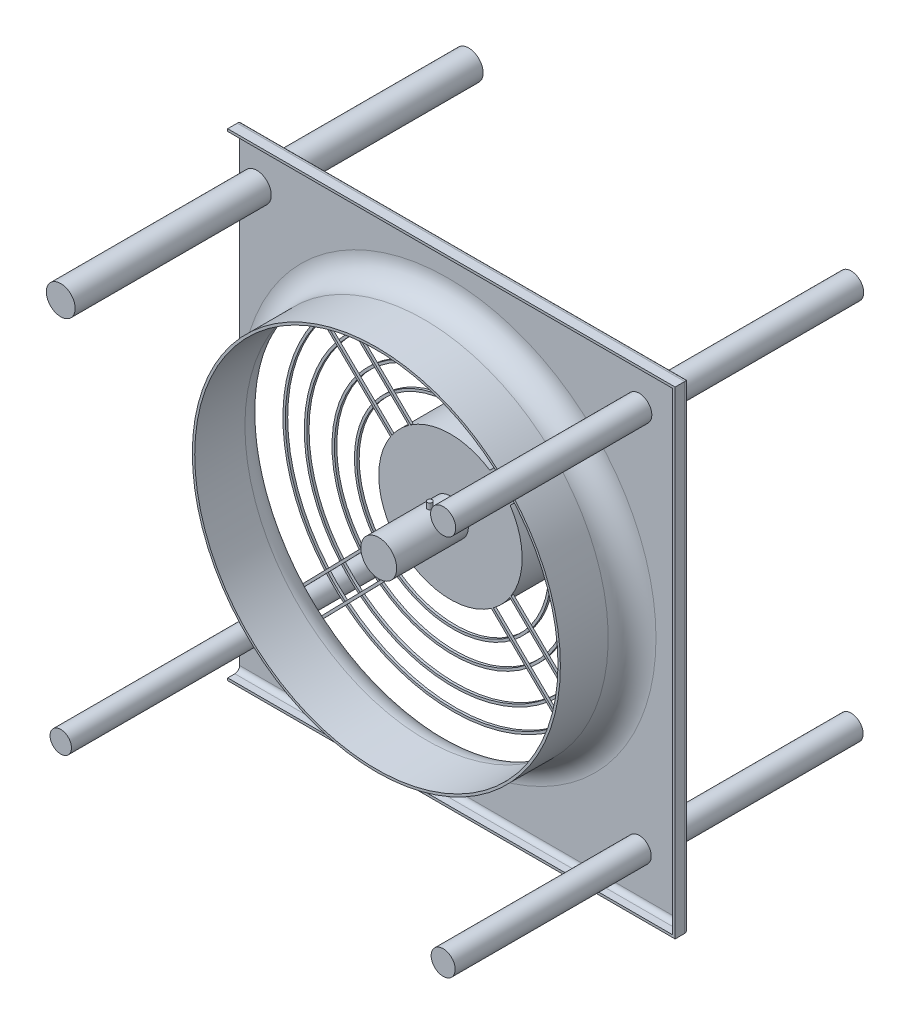
SolidWorks part; units mm, degrees
ref_plane "Front Plane" through (0, 0, 0) normal (0, 0, 1) x (1, 0, 0)
ref_plane "Top Plane" through (0, 0, 0) normal (0, 1, 0) x (1, 0, 0)
ref_plane "Right Plane" through (0, 0, 0) normal (1, 0, 0) x (0, 0, -1)
sketch "Sketch1" plane through (0, 0, 0) normal (0, 0, 1) x (1, 0, 0)
  line L1 (-100, -100) -> (100, -100)
  line L2 (-100, -100) -> (-100, 100)
  line L3 (-100, 100) -> (100, 100)
  line L4 (100, -100) -> (100, 100)
  line L5 (-100, -100) -> (100, 100) construction
  line L6 (-100, 100) -> (100, -100) construction
  circle A0 centre (0, 0) radius 76
  point P0 (0, 0)
  dimension "D2" = 152
  dimension "D1" = 200
extrude "Boss-Extrude1" add sketch "Sketch1" along normal blind 1
sketch "Sketch2" plane through (0, 0, 1) normal (0, 0, 1) x (1, 0, 0)
  line L4 (100, -100) -> (100, 100)
  line L5 (100, 100) -> (-100, 100)
  line L6 (-100, 100) -> (-100, -100)
  line L7 (-100, -100) -> (100, -100)
  line L8 (100, -100) -> (100, 100)
  line L9 (100, 100) -> (-100, 100)
  line L10 (-100, 100) -> (-100, -100)
  line L11 (-100, -100) -> (100, -100)
  line L16 (99, -99) -> (99, 99)
  line L17 (99, 99) -> (-99, 99)
  line L18 (-99, 99) -> (-99, -99)
  line L19 (-99, -99) -> (99, -99)
  line L20 (99, -99) -> (99, 99)
  line L21 (99, 99) -> (-99, 99)
  line L22 (-99, 99) -> (-99, -99)
  line L23 (-99, -99) -> (99, -99)
  dimension "D1" = 0
  dimension "D2" = 1
extrude "Boss-Extrude2" add sketch "Sketch2" along normal blind 5
fillet "Fillet1" radius 2 4 edges at (0, -99, 1) (99, 0, 1) (0, 99, 1) (-99, 0, 1)
fillet "Fillet2" radius 2 4 edges at (-100, 0, 0) (0, 100, 0) (100, 0, 0) (0, -100, 0)
sketch "Sketch3" plane through (0, 0, 1) normal (0, 0, 1) x (1, 0, 0)
  circle A0 centre (0, 0) radius 76 construction
  circle A1 centre (0, 0) radius 76
  circle A4 centre (0, 0) radius 77
  circle A5 centre (0, 0) radius 77
  dimension "D1" = 1
extrude "Boss-Extrude3" add sketch "Sketch3" along normal blind 30
fillet "Fillet3" radius 10 2 edges at (76, 0, 0) (-77, 0, 1)
hole_wizard "Ø4.0 (4) Diameter Hole1" positions "Sketch5" profile "Sketch6" hole size "Ø4.0" standard "DIN" end condition through all
sketch "Sketch5" plane through (0, 0, 0) normal (0, 0, -1) x (-1, 0, 0)
  line L1 (-80, 80) -> (80, 80) construction
  line L2 (-80, 80) -> (-80, -80) construction
  line L3 (-80, -80) -> (80, -80) construction
  line L4 (80, 80) -> (80, -80) construction
  line L5 (-80, 80) -> (80, -80) construction
  line L6 (-80, -80) -> (80, 80) construction
  point P0 (80, 80)
  point P2 (80, -80)
  point P4 (-80, -80)
  point P6 (-80, 80)
  point P8 (0, 0)
  dimension "D1" = 160
sketch "Sketch6" plane through (-80, 80, 0) normal (1, 0, 0) x (0, 1, 0)
  line L0 (0, 0) -> (0, 31)
  line L1 (0, 31) -> (2, 31)
  line L2 (2, 31) -> (2, 0)
  line L5 (2, 0) -> (0, 0)
  line L11 (0, -6.35) -> (0, 107.95) construction
  dimension "Thru Hole Dia." = 4
  dimension "Thru Hole Depth" = 31
sketch "Sketch7" plane through (0, 0, 0) normal (0, 0, -1) x (-1, 0, 0)
  circle A0 centre (0, 0) radius 30
  dimension "D1" = 60
extrude "Boss-Extrude4" add sketch "Sketch7" along normal blind 42 separate body
fillet "Fillet4" radius 5 1 edges at (-30, 0, -42)
sketch "Sketch8" plane through (0, 0, 0) normal (0, 0, 1) x (1, 0, 0)
  circle A0 centre (0, 0) radius 7.5
  dimension "D1" = 15
extrude "Boss-Extrude5" add sketch "Sketch8" along normal blind 30
sketch "Sketch9" plane through (0, 0, 30) normal (0, 0, 1) x (1, 0, 0)
  circle A0 centre (0, 0) radius 24.9716
sketch "Sketch13" plane through (0, 0, 0) normal (0, 0, -1) x (-1, 0, 0)
  line L0 (64.9936, 70.7743) -> (-73.8337, -64.6251)
  line L1 (-66.8515, -71.784) -> (71.9757, 63.6154)
  line L2 (71.9757, 63.6154) -> (64.9936, 70.7743)
  line L3 (-73.8337, -64.6251) -> (-66.8515, -71.784)
  line L4 (80, 78) -> (-82, -80) construction
  circle A0 centre (80, 80) radius 2 construction
  circle A1 centre (-80, -80) radius 2 construction
  dimension "D1" = 10
extrude "Extrude-Thin1" add sketch "Sketch13" along normal blind 1 thin
pattern_circular "CirPattern2" count 2 over 90 about axis through (0, 0, 0) along (0, 0, 1) of "Extrude-Thin1"
sketch "Sketch14" plane through (0, 0, -1) normal (0, 0, -1) x (-1, 0, 0)
  circle A0 centre (0, 0) radius 40.1817
  circle A1 centre (0, 0) radius 49.5662
  circle A2 centre (0, 0) radius 61.1586
  circle A3 centre (0, 0) radius 70.0948
  circle A4 centre (0, 0) radius 89.3407
extrude "Extrude-Thin2" add sketch "Sketch14" along normal blind 1 thin contours A0 | A1 | A2 | A3 | A4
scale "Scale1" bodies to scale 111 109 113 108 112 110 114 117 scale about centroid uniform scaling yes scale factor 2
sketch "Sketch15" plane through (0, 0, 24.7166) normal (0, 0, 1) x (1, 0, 0)
  line L0 (-178.1547, 331.8105) -> (-178.1547, -384.2597)
  line L1 (-178.1547, -571.4964) -> (-178.1547, 355.6036) construction
  line L2 (-178.1547, -571.4964) -> (-178.1547, 355.6036) construction
  line L3 (-178.1547, -384.2597) -> (-249.859, -384.2597)
  line L4 (-249.859, -384.2597) -> (-249.859, 331.8105)
  line L5 (-249.859, 331.8105) -> (-178.1547, 331.8105)
  line L6 (202.8453, 355.6036) -> (202.8453, -571.4964) construction
  line L7 (202.8453, 323.2127) -> (236.5283, 323.2127)
  line L8 (202.8453, 323.2127) -> (202.8453, -313.0212)
  line L9 (202.8453, -313.0212) -> (236.5283, -313.0212)
  line L10 (236.5283, 323.2127) -> (236.5283, -313.0212)
extrude "Cut-Extrude1" cut sketch "Sketch15" against normal blind 672.066
sketch "Sketch16" plane through (0, 0, 14.7166) normal (0, 0, 1) x (1, 0, 0)
  circle A0 centre (-160.0008, 160.0036) radius 12.0643
  circle A1 centre (159.9992, 160.0036) radius 10.5019
  circle A2 centre (-160.0008, -159.9964) radius 8.9546
  circle A3 centre (159.9992, -159.9964) radius 10.0445
extrude "Boss-Extrude7" add sketch "Sketch16" along normal up to surface (164.1 mm away) and the other way up to surface (177.3019 mm away)
sketch "Sketch17" plane through (0, 0, 12.7166) normal (0, 0, -1) x (-1, 0, 0)
  line L1 (174.4126, 215.1632) -> (255.2189, 215.1632)
  line L2 (174.4126, 215.1632) -> (174.4126, -233.9511)
  line L3 (174.4126, -233.9511) -> (255.2189, -233.9511)
  line L4 (255.2189, 215.1632) -> (255.2189, -233.9511)
extrude "Cut-Extrude2" cut sketch "Sketch17" against normal blind 38
sketch "Sketch18" plane through (0, 0, 0) normal (0, 1, 0) x (1, 0, 0)
  circle A0 centre (0, -30) radius 2
  dimension "D1" = 4
extrude "Boss-Extrude8" add sketch "Sketch18" along normal blind 20
